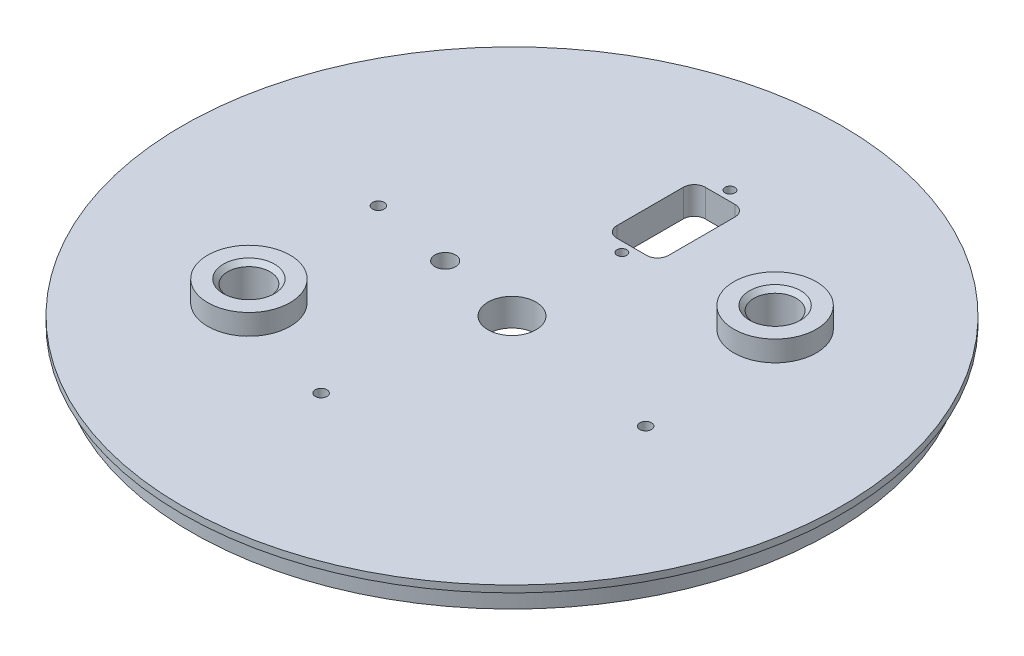
SolidWorks part; units mm, degrees
material "Delrin 2700 NC010, Low Viscosity Acetal Copolymer (SS)"
ref_plane "Front Plane" through (0, 0, 0) normal (0, 0, 1) x (1, 0, 0)
ref_plane "Top Plane" through (0, 0, 0) normal (0, 1, 0) x (1, 0, 0)
ref_plane "Right Plane" through (0, 0, 0) normal (1, 0, 0) x (0, 0, -1)
sketch "Sketch1" plane through (0, 0, 0) normal (0, 1, 0) x (1, 0, 0)
  circle A0 centre (0, 0) radius 76.2
  dimension "D1" = 152.4
extrude "Boss-Extrude1" add sketch "Sketch1" along normal blind 11.1125
hole_wizard "Tap Drill for #4-40 Tap1" positions "Sketch3" profile "Sketch4" hole size "#4-40" standard "ANSI Inch" end condition through all
sketch "Sketch3" plane through (0, 0, 0) normal (0, -1, 0) x (-1, 0, 0)
  point P0 (0, 25.4)
  point P2 (0, 50.4)
  point P6 (0, 0)
  dimension "D1" = 25.4
  dimension "D2" = 25
sketch "Sketch4" plane through (0, 0, -25.4) normal (1, 0, 0) x (0, 0, -1)
  line L0 (0, 0) -> (0, 11.1125)
  line L1 (0, 11.1125) -> (1.1303, 11.1125)
  line L2 (1.1303, 11.1125) -> (1.1303, 0)
  line L5 (1.1303, 0) -> (0, 0)
  line L11 (0, -6.35) -> (0, 107.95) construction
  dimension "Thru Hole Dia." = 2.2606
  dimension "Thru Hole Depth" = 11.1125
sketch "Sketch2" plane through (0, 0, 0) normal (0, -1, 0) x (1, 0, 0)
  line L0 (0, 0) -> (0, -55.372) construction
  line L1 (-3.429, -27.686) -> (3.429, -27.686)
  line L2 (-5.969, -30.226) -> (-5.969, -45.574)
  line L3 (-3.429, -48.114) -> (3.429, -48.114)
  line L4 (5.969, -30.226) -> (5.969, -45.574)
  arc A0 (3.429, -48.114) -> (5.969, -45.574) centre (3.429, -45.574) ccw
  arc A1 (-5.969, -45.574) -> (-3.429, -48.114) centre (-3.429, -45.574) ccw
  arc A2 (3.429, -27.686) -> (5.969, -30.226) centre (3.429, -30.226) cw
  arc A3 (-3.429, -27.686) -> (-5.969, -30.226) centre (-3.429, -30.226) ccw
  circle A4 centre (0, -25.4) radius 1.1303 construction
  circle A5 centre (0, -50.4) radius 1.1303 construction
  point P10 (5.969, -27.686)
  point P13 (-5.969, -27.686)
  point P17 (0, -27.686)
  dimension "D2" = 2.54
  dimension "D1" = 11.938
  dimension "D3" = 2.286
  dimension "D4" = 2.286
extrude "Cut-Extrude1" cut sketch "Sketch2" against normal through all
hole_wizard "Tap Drill for #6-32 Tap1" positions "Sketch5" profile "Sketch6" hole size "#6-32" standard "ANSI Inch" end condition through all
sketch "Sketch5" plane through (0, 0, 0) normal (0, -1, 0) x (-1, 0, 0)
  line L0 (0, 0) -> (58.3519, 0) construction
  line L2 (0, 0) -> (37.5212, 6.616) construction
  point P0 (37.5212, 6.616)
  dimension "D1" = 10
  dimension "D2" = 38.1
sketch "Sketch6" plane through (-37.5212, 0, -6.616) normal (1, 0, 0) x (0, 0, -1)
  line L0 (0, 0) -> (0, 11.1125)
  line L1 (0, 11.1125) -> (1.3525, 11.1125)
  line L2 (1.3525, 11.1125) -> (1.3525, 0)
  line L5 (1.3525, 0) -> (0, 0)
  line L11 (0, -6.35) -> (0, 107.95) construction
  dimension "Thru Hole Dia." = 2.7051
  dimension "Thru Hole Depth" = 11.1125
pattern_circular "CirPattern1" count 4 over 360 about axis through (0, 0, 0) along (0, 1, 0) skipping 3 of "Tap Drill for #6-32 Tap1"
hole_wizard "W (0.386) Diameter Hole1" positions "Sketch7" profile "Sketch8" hole size "W" standard "ANSI Inch" end condition through all
sketch "Sketch7" plane through (0, 0, 0) normal (0, -1, 0) x (-1, 0, 0)
  line L2 (0, 0) -> (-33.0778, 27.7556) construction
  line L4 (0, 0) -> (0, 19.4817) construction
  point P0 (-33.0778, 27.7556)
  point P17 (33.0778, -27.7556)
  dimension "D1" = 50
  dimension "D2" = 43.18
  dimension "D3" = 43.18
sketch "Sketch8" plane through (33.0778, 0, -27.7556) normal (1, 0, 0) x (0, 0, -1)
  line L0 (0, 0) -> (0, 11.1125)
  line L1 (0, 11.1125) -> (4.9022, 11.1125)
  line L2 (4.9022, 11.1125) -> (4.9022, 0)
  line L5 (4.9022, 0) -> (0, 0)
  line L11 (0, -6.35) -> (0, 107.95) construction
  dimension "Thru Hole Dia." = 9.8044
  dimension "Thru Hole Depth" = 11.1125
hole_wizard "3/16 (0.1875) Diameter Hole1" positions "Sketch10" profile "Sketch11" hole size "3/16" standard "ANSI Inch" end condition through all
sketch "Sketch10" plane through (0, 0, 0) normal (0, -1, 0) x (-1, 0, 0)
  line L0 (0, 0) -> (37.5212, 6.616) construction
  point P0 (18.7606, 3.308)
  point P9 (18.7606, 3.308)
sketch "Sketch11" plane through (-18.7606, 0, -3.308) normal (1, 0, 0) x (0, 0, -1)
  line L0 (0, 0) -> (0, 11.1125)
  line L1 (0, 11.1125) -> (2.3812, 11.1125)
  line L2 (2.3812, 11.1125) -> (2.3812, 0)
  line L5 (2.3812, 0) -> (0, 0)
  line L11 (0, -6.35) -> (0, 107.95) construction
  dimension "Thru Hole Dia." = 4.7625
  dimension "Thru Hole Depth" = 11.1125
sketch "Sketch12" plane through (0, 0, 0) normal (0, -1, 0) x (1, 0, 0)
  line L0 (0, 0) -> (31.6547, 37.7246) construction
  line L10 (19.8869, 28.7385) -> (24.8486, 24.5751)
  line L11 (19.8869, 28.7385) -> (6.4989, 12.7833)
  line L12 (6.4989, 12.7833) -> (11.4606, 8.62)
  line L13 (24.8486, 24.5751) -> (11.4606, 8.62)
  line L17 (0, 0) -> (-53.1972, 0) construction
  line L18 (-33.0778, 27.7556) -> (33.0778, -27.7556) construction
  circle A0 centre (22.3677, 26.6568) radius 3.2385
  circle A1 centre (8.9797, 10.7016) radius 3.2385
  circle A2 centre (33.0778, -27.7556) radius 4.9022 construction
  circle A3 centre (-33.0778, 27.7556) radius 4.9022 construction
  circle A4 centre (33.0778, -27.7556) radius 4.9022
  circle A5 centre (-33.0778, 27.7556) radius 4.9022
  dimension "D1" = 6.477
  dimension "D2" = 13.97
  dimension "D3" = 20.828
extrude "Cut-Extrude4" cut sketch "Sketch12" against normal blind 3.175 contours A1 L13 A0 L11 | L10 A0 | L12 A1 | L12 A1 | L10 A0 region at (23.2512, 0, 27.7097) region at (15.6737, 0, 18.6792) region at (21.4842, 0, 25.6039) region at (9.8632, 0, 11.7545) region at (8.0963, 0, 9.6487)
ref_plane "Plane1" through (0, 0, 0) normal (0.6428, 0, 0.766) x (0.766, 0, -0.6428)
mirror "Mirror1" about plane through (0, 0, 0) normal (0.6428, 0, 0.766) of "Cut-Extrude4"
hole_wizard "7/16 (0.4375) Diameter Hole1" positions "Sketch13" profile "Sketch14" hole size "7/16" standard "ANSI Inch" end condition through all
sketch "Sketch13" plane through (0, 0, 0) normal (0, -1, 0) x (-1, 0, 0)
  point P0 (0, 0)
sketch "Sketch14" plane through (0, 0, 0) normal (1, 0, 0) x (0, 0, -1)
  line L0 (0, 0) -> (0, 11.1125)
  line L1 (0, 11.1125) -> (5.5562, 11.1125)
  line L2 (5.5562, 11.1125) -> (5.5562, 0)
  line L5 (5.5562, 0) -> (0, 0)
  line L11 (0, -6.35) -> (0, 107.95) construction
  dimension "Thru Hole Dia." = 11.1125
  dimension "Thru Hole Depth" = 11.1125
sketch "Sketch15" plane through (0, 0, 0) normal (0, -1, 0) x (1, 0, 0)
  circle A0 centre (0, 0) radius 74.041
  circle A1 centre (0, 0) radius 76.2 construction
  circle A2 centre (0, 0) radius 76.2
  dimension "D1" = 148.082
extrude "Cut-Extrude5" cut sketch "Sketch15" against normal blind 4.7625
sketch "Sketch17" plane through (0, 11.1125, 0) normal (0, 1, 0) x (1, 0, 0)
  circle A0 centre (-33.0778, -27.7556) radius 9.525
  circle A1 centre (33.0778, 27.7556) radius 9.525
  dimension "D1" = 19.05
  dimension "D2" = 19.05
split line "Split Line1"
sketch "Sketch19" plane through (0, 0, 0) normal (0, -1, 0) x (1, 0, 0)
  circle A0 centre (-33.0778, 27.7556) radius 9.525
  circle A1 centre (33.0778, -27.7556) radius 9.525
  dimension "D1" = 19.05
  dimension "D2" = 19.05
split line "Split Line2"
chamfer "Chamfer2" distance 1.016 angle 45 4 edges at (-33.0778, 0, 22.8534) (33.0778, 0, -32.6578) (-33.0778, 11.1125, 22.8534) (33.0778, 11.1125, -32.6578)
sketch "Sketch18" plane through (0, 11.1125, 0) normal (0, 1, 0) x (1, 0, 0)
  circle A0 centre (0, 0) radius 76.2 construction
  circle A1 centre (33.0778, 27.7556) radius 9.525 construction
  circle A2 centre (-33.0778, -27.7556) radius 9.525 construction
  circle A3 centre (0, 0) radius 76.2
  circle A4 centre (33.0778, 27.7556) radius 9.525
  circle A5 centre (-33.0778, -27.7556) radius 9.525
  circle M2 centre (-33.0778, -27.7556) radius 9.525
  circle M3 centre (0, 0) radius 5.5562
  circle M4 centre (-18.7606, 3.308) radius 2.3812
  circle M5 centre (0, 0) radius 76.2
  circle M6 centre (0, 50.4) radius 1.1303
  circle M7 centre (0, 25.4) radius 1.1303
  arc M8 (3.429, 48.114) -> (5.969, 45.574) centre (3.429, 45.574) cw
  line M9 (5.969, 45.574) -> (5.969, 30.226)
  arc M10 (5.969, 30.226) -> (3.429, 27.686) centre (3.429, 30.226) cw
  line M11 (3.429, 27.686) -> (-3.429, 27.686)
  arc M12 (-3.429, 27.686) -> (-5.969, 30.226) centre (-3.429, 30.226) cw
  line M13 (-5.969, 30.226) -> (-5.969, 45.574)
  arc M14 (-5.969, 45.574) -> (-3.429, 48.114) centre (-3.429, 45.574) cw
  line M15 (-3.429, 48.114) -> (3.429, 48.114)
  circle M16 centre (-37.5212, 6.616) radius 1.3525
  circle M17 centre (-6.616, -37.5212) radius 1.3525
  circle M18 centre (37.5212, -6.616) radius 1.3525
  circle M19 centre (33.0778, 27.7556) radius 9.525
extrude "Cut-Extrude6" cut sketch "Sketch18" against normal blind 4.7625 contours M5 M3 M7 M17 M19 M18 M16 M15 M8 M9 M10 M11 M12 M13 M14 M6 M4 M2 region at (-74.0447, 11.1125, 0)
equation "\"Bodytube_OD\" = 6.17in"
equation "\"Bodytube_ID\" = 5.998in"
equation "\"Camera_Cutout_Width\"=10mm"
equation "\"Camera_Cutout_Height\"=7mm"
equation "\"Fwd_Tube_Length\" = 40in"
equation "\"BKHD_Screw_Diam\"= 3.5mm"
equation "\"Fwd_BKHD_From_Top\" = 18in"
equation "\"Shear_Screw_Diameter\" = 0.086in"
equation "\"Shear_Screw_Coupler_Location\" = 4.5in"
equation "\"Motor_OD\" = 4in"
equation "\"Mid_Coupler_Length\" = 13in"
equation "\"Aft_Section_Length\"= 39in"
equation "\"AB_Coupler_OD_Length\"= 1in"
equation "\"AB_Coupling_Section_Length\"= 0.375in"
equation "\"AB_Coupler_Length\"= \"AB_Coupler_OD_Length\" + \"AB_Coupling_Section_Length\" * 2"
equation "\"Cutout_Angle\" = 80"
equation "\"AB_Paddle_Height\" = 0.375in"
equation "\"AB_Coupler_Num_Screws\"= 4"
equation "\"AB_BKHD_Thickness\" = 0.375in"
equation "\"AB_Mount_From_Bottom\" = 23.175in"
equation "\"Num_Cutouts\" = 3"
equation "\"AB_Coupler_OD\"= 6.17in"
equation "\"AB_Coupler_ID\"= 5.75in"
equation "\"AB_Coupler_Surface_Diameter\"= 5.998in"
equation "\"AB_Coupling_Screw_Diameter\"= 0.15748in"
equation "\"AB_Central_Bushing_Length\" = .4724in"
equation "\"Lead_Screw_Dist\" = 3.4in"
equation "\"Lead_Screw_Diam\" = 0.386in"
equation "\"Lead_Screw_Length\" = (\"Mid_Coupler_Length\" + 2*0.375in + 2*0.5in)"
equation "\"Paddle_Pin_Offset\" = .25in"
equation "\"Paddle_Pin_Radius\" = 2.25in"
equation "\"SS_Paddle_Pin_Radius\" = 2.25*0.66in"
equation "\"Paddle_Gear_OD\" = 3.2in"
equation "\"Drive_Gear_OD\" = 1.7in"
equation "\"Fin_Thickness\"= .118in"
equation "\"Guiderail_Cutout_Diameter\"= 1.5in"
equation "\"DB9_Hole_Dist\" = 25mm"
equation "\"DB9_Relief_Width\" = 0.47in"
equation "\"DB9_Relief_Hole_Offset\" = 0.09in"
equation "\"Airbrakes_Wire_Hole_Dia\" = .25in"
equation "\"Airbrakes_Wire_Hole_Dist\" = 1.1in"
equation "\"Servo_Gear_Offset\" = 0.5in"
equation "\"FWD_Shear_Screw_Dist\" = 1.5in"
equation "\"Camera_Screw_Dia\" = 0.216535"
equation "\"Camera_Hole_Angle\" = atn ( 2 / 3 * tan ( 12.5deg ) )"
equation "\"Coupler_OD\" = 5.998"
equation "\"Coupler_ID\" = 5.8"
equation "\"Mounting_Bracket_Centerhole_DIA\" = 0.4in"
equation "\"Drive_Gear_Shaft_DIA\" = \"Mounting_Bracket_Centerhole_DIA\" - 0.02in"
equation "\"Drive_Gear_Fillet\" = 0.22in"
equation "\"Drive_Gear_ID\" = 0.62in"
equation "\"Drive_Gear_Offset\" = 0.01in"
equation "\"D1@Sketch2\"=\"DB9_Relief_Width\""
equation "\"D2@Sketch3\"=\"DB9_Hole_Dist\""
equation "\"D3@Sketch2\"=\"DB9_Relief_Hole_Offset\""
equation "\"D4@Sketch2\"=\"DB9_Relief_Hole_Offset\""
equation "\"D2@Sketch7\"=\"Lead_Screw_Dist\"/2"
equation "\"D3@Sketch7\"=\"Lead_Screw_Dist\"/2"
